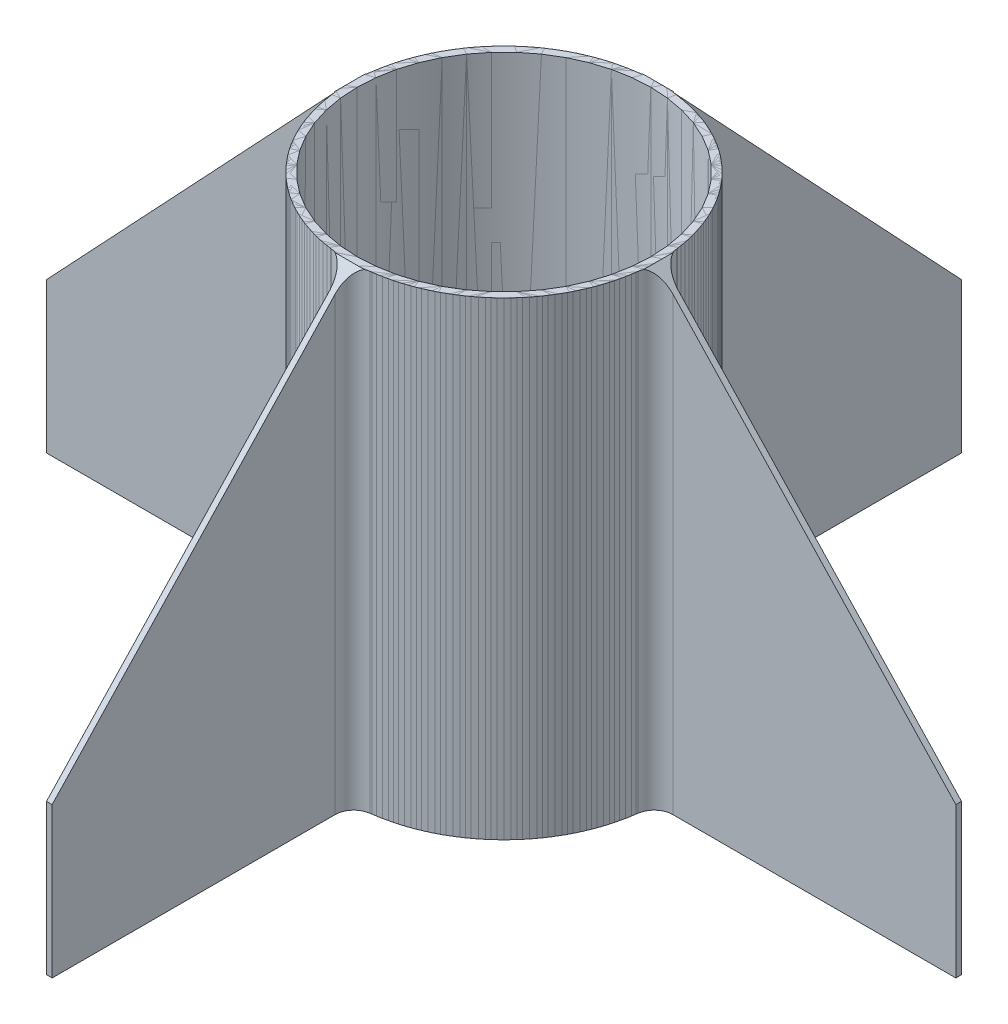
SolidWorks part; units mm, degrees
material "Commercially Pure grade 2 longitudinal (SS)"
ref_plane "Front Plane" through (0, 0, 0) normal (0, 0, 1) x (1, 0, 0)
ref_plane "Top Plane" through (0, 0, 0) normal (0, 1, 0) x (1, 0, 0)
ref_plane "Right Plane" through (0, 0, 0) normal (1, 0, 0) x (0, 0, -1)
sketch "Sketch1" plane through (0, 0, 0) normal (0, 1, 0) x (1, 0, 0)
  circle A0 centre (0, 0) radius 82.2
  circle A1 centre (0, 0) radius 78.2
  dimension "D1" = 164.4
  dimension "D2" = 156.4
extrude "Boss-Extrude1" add sketch "Sketch1" along normal blind 250
sketch "Sketch2" plane through (0, 0, 0) normal (0, 0, 1) x (1, 0, 0)
  line L0 (82.2, 0) -> (82.2, 250) construction
  line L1 (82.2, 0) -> (82.2, 250)
  line L2 (82.2, 0) -> (242.2, 0)
  line L3 (242.2, 0) -> (242.2, 80)
  line L4 (242.2, 80) -> (82.2, 250)
  dimension "D1" = 160
  dimension "D2" = 80
extrude "Boss-Extrude2" add sketch "Sketch2" along normal blind 1.5 and the other way blind 1.5 separate body
sketch "Sketch4" plane through (0, 0, 0) normal (0, 0, 1) x (1, 0, 0)
  line L0 (82.2, 250) -> (82.2, 0) construction
  line L1 (82.2, 250) -> (82.2, 0)
  line L2 (82.2, 250) -> (80.2, 250)
  line L3 (82.2, 250) -> (-82.2, 250) construction
  line L4 (80.2, 250) -> (80.2, 0)
  line L5 (-82.2, 0) -> (82.2, 0) construction
  line L6 (80.2, 0) -> (82.2, 0)
  point P2 (82.2, 125)
  dimension "D1" = 2
extrude "Boss-Extrude3" add sketch "Sketch4" along normal blind 1.5 and the other way blind 1.5
fillet "Fillet1" radius 10 2 edges at (82.1863, 125, -1.5) (82.1863, 125, 1.5)
pattern_circular "CirPattern1" count 4 over 360 about axis through (0, 250, 0) along (0, -1, 0) of bodies 103
